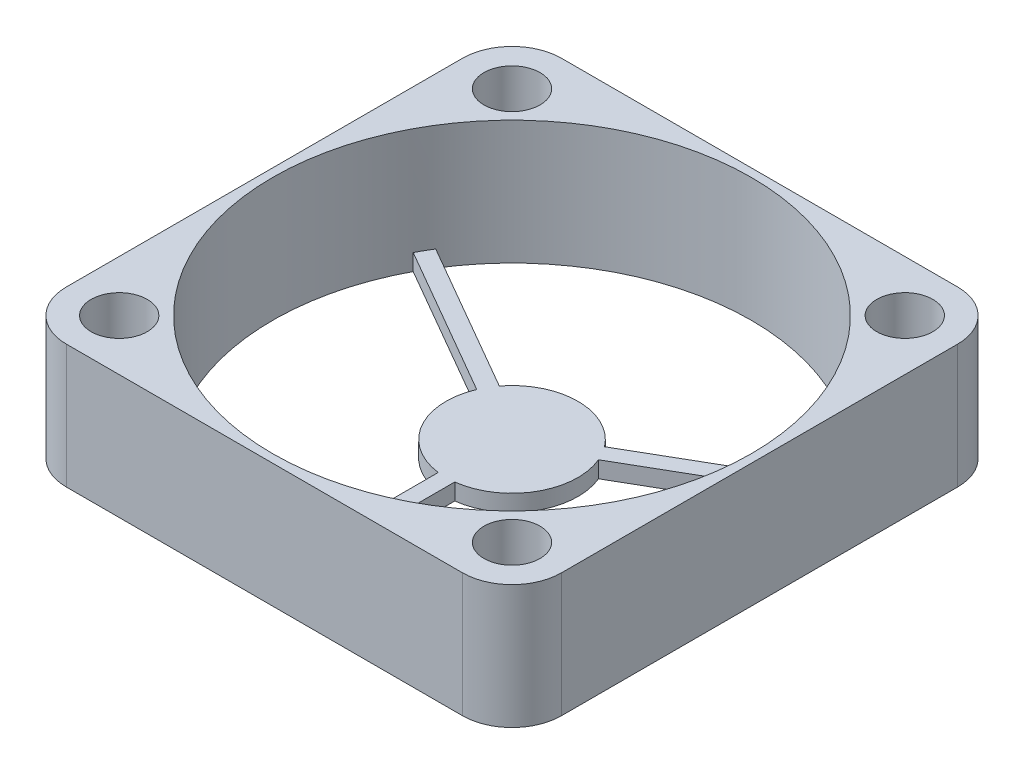
SolidWorks part; units mm, degrees
ref_plane "Front Plane" through (0, 0, 0) normal (0, 0, 1) x (1, 0, 0)
ref_plane "Top Plane" through (0, 0, 0) normal (0, 1, 0) x (1, 0, 0)
ref_plane "Right Plane" through (0, 0, 0) normal (1, 0, 0) x (0, 0, -1)
sketch "Sketch1" plane through (0, 0, 0) normal (0, 1, 0) x (1, 0, 0)
  line L0 (-11.9, 11.9) -> (11.9, 11.9) construction
  line L1 (-12, -15) -> (12, -15)
  line L2 (-15, -12) -> (-15, 12)
  line L3 (-12, 15) -> (12, 15)
  line L4 (15, -12) -> (15, 12)
  line L5 (-15, -15) -> (15, 15) construction
  line L6 (-15, 15) -> (15, -15) construction
  line L7 (11.9, 11.9) -> (11.9, -11.9) construction
  line L8 (11.9, -11.9) -> (-11.9, -11.9) construction
  line L9 (-11.9, -11.9) -> (-11.9, 11.9) construction
  line L10 (-2.1341, 11.9) -> (-2.1341, 15) construction
  line L11 (0, -11.9) -> (0, -15) construction
  line L12 (11.9, 0) -> (15, 0) construction
  line L13 (-11.9, 0) -> (-15, 0) construction
  arc A0 (-12, -15) -> (-15, -12) centre (-12, -12) cw
  arc A1 (15, 12) -> (12, 15) centre (12, 12) ccw
  arc A2 (12, -15) -> (15, -12) centre (12, -12) ccw
  arc A3 (-12, 15) -> (-15, 12) centre (-12, 12) ccw
  circle A4 centre (-11.9, 11.9) radius 1.7
  circle A5 centre (11.9, 11.9) radius 1.7
  circle A6 centre (11.9, -11.9) radius 1.7
  circle A7 centre (-11.9, -11.9) radius 1.7
  point P0 (0, 0)
  dimension "D3" = 3
  dimension "D6" = 3.4
  dimension "D1" = 30
  dimension "D2" = 30
  dimension "D4" = 23.8
  dimension "D5" = 23.8
extrude "Boss-Extrude1" add sketch "Sketch1" along normal blind 7.5
sketch "Sketch2" plane through (0, 7.5, 0) normal (0, 1, 0) x (1, 0, 0)
  circle A0 centre (0, 0) radius 14.5
  dimension "D1" = 29
extrude "Cut-Extrude1" cut sketch "Sketch2" against normal blind 7.5 contours A0
sketch "Sketch3" plane through (0, 0, 0) normal (0, -1, 0) x (1, 0, 0)
  circle A0 centre (0, 0) radius 4
  dimension "D1" = 8
extrude "Boss-Extrude2" add sketch "Sketch3" against normal blind 1 separate body
sketch "Sketch4" plane through (0, 0, 0) normal (0, -1, 0) x (1, 0, 0)
  line L0 (0, 4) -> (0, 14.5) construction
  line L1 (-0.5, 14.4914) -> (-0.5, 3.9686)
  line L2 (0.5, 14.4914) -> (0.5, 3.9686)
  line L3 (-0.5, 9.23) -> (0, 9.23) construction
  line L4 (0, 9.23) -> (0.5, 9.23) construction
  line L5 (12.2999, -7.6787) -> (3.1869, -2.4173)
  line L6 (12.7999, -6.8127) -> (3.6869, -1.5513)
  line L7 (-12.7999, -6.8127) -> (-3.6869, -1.5513)
  line L8 (-12.2999, -7.6787) -> (-3.1869, -2.4173)
  circle A0 centre (0, 0) radius 4 construction
  circle A1 centre (0, 0) radius 14.5 construction
  arc A2 (-0.5, 3.9686) -> (0.5, 3.9686) centre (0, 0) cw
  arc A3 (-0.5, 14.4914) -> (0.5, 14.4914) centre (0, 0) cw
  arc A4 (12.7999, -6.8127) -> (12.2999, -7.6787) centre (0, 0) cw
  arc A5 (3.6869, -1.5513) -> (3.1869, -2.4173) centre (0, 0) cw
  arc A6 (-12.2999, -7.6787) -> (-12.7999, -6.8127) centre (0, 0) cw
  arc A7 (-3.1869, -2.4173) -> (-3.6869, -1.5513) centre (0, 0) cw
  point P26 (0, 0)
  dimension "D1" = 0.5
  dimension "D2" = 3
extrude "Boss-Extrude3" add sketch "Sketch4" against normal up to surface (1 mm away) up to face at (0, 1, -4)
